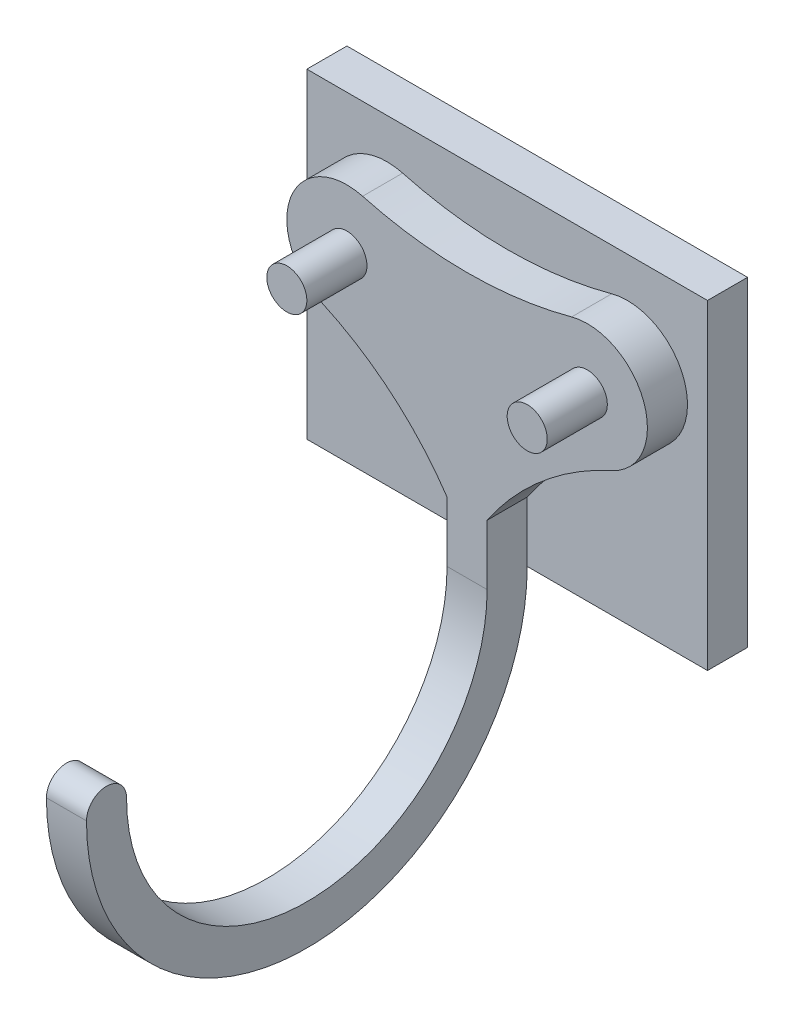
SolidWorks part; units mm, degrees
ref_plane "Front Plane" through (0, 0, 0) normal (0, 0, 1) x (1, 0, 0)
ref_plane "Top Plane" through (0, 0, 0) normal (0, 1, 0) x (1, 0, 0)
ref_plane "Right Plane" through (0, 0, 0) normal (1, 0, 0) x (0, 0, -1)
sketch "Sketch1" plane through (0, 0, 0) normal (0, 0, 1) x (1, 0, 0)
  line L0 (0, 0) -> (0, 12222.5331) construction
  line L1 (0, 0) -> (-12222.5331, 0) construction
  line L3 (-10, -8) -> (10, -8)
  line L4 (-10, -8) -> (-10, 8)
  line L5 (-10, 8) -> (10, 8)
  line L6 (10, -8) -> (10, 8)
  line L7 (-10, -8) -> (10, 8) construction
  line L8 (-10, 8) -> (10, -8) construction
  line L9 (-1, -8) -> (1, -8)
  line L10 (-1, -8) -> (-1, -5)
  line L12 (1, -8) -> (1, -5)
  line L13 (-1, -8) -> (1, -5) construction
  line L14 (-1, -5) -> (1, -8) construction
  circle A0 centre (6, 3) radius 1
  circle A1 centre (-6, 3) radius 1
  arc A2 (6, 0) -> (5.2174, 5.8961) centre (6, 3) ccw
  arc A3 (-5.2174, 5.8961) -> (-6, 0) centre (-6, 3) ccw
  arc A4 (-5.2174, 5.8961) -> (5.2174, 5.8961) centre (0, 25.2036) ccw
  arc A5 (-7.2385, 0.2676) -> (-1, -5) centre (-13.4311, -13.3945) cw
  arc A6 (7.2385, 0.2676) -> (1, -5) centre (13.4311, -13.3945) ccw
  point P14 (0, 0)
  point P22 (0, -6.5)
  dimension "D1" = 2
  dimension "D2" = 2
  dimension "D5" = 6
  dimension "D6" = 6
  dimension "D7" = 20
  dimension "D8" = 16
  dimension "D14" = 15
  dimension "D3" = 6
  dimension "D4" = 6
  dimension "D9" = 20
  dimension "D10" = 5
  dimension "D11" = 2
  dimension "D12" = 0
  dimension "D13" = 3
extrude "Boss-Extrude2" add sketch "Sketch1" along normal blind 2 contours A2 A6 L12 L3 L6 L5 L4 L10 A5 A3 A4 region at (-9.7439, 0, 0)
extrude "Boss-Extrude3" add sketch "Sketch1<5>" along normal blind 4 contours A6 A2 A4 A3 A5 L10 L3 L12 A1 A0 region at (0, 1.1623, 0)
sketch "Sketch1<5>" plane through (0, 0, 0) normal (0, 0, 1) x (1, 0, 0) same geometry as "Sketch1"
extrude "Boss-Extrude4" add sketch "Sketch1<6>" along normal blind 7 contours A1 | A0 region at (6, 3, 0) region at (-6, 3, 0)
sketch "Sketch1<6>" plane through (0, 0, 0) normal (0, 0, 1) x (1, 0, 0) same geometry as "Sketch1"
ref_plane "Plane1" through (0, 0, 13) normal (0, 0, 1) x (1, 0, 0)
ref_plane "Plane2" through (0, -8, 0) normal (0, -1, 0) x (-1, 0, 0)
ref_axis "Axis1" through (-9.9, -8, 13) along (1, 0, 0)
sketch "Sketch2" plane through (0, -8, 0) normal (0, -1, 0) x (1, 0, 0)
  line L0 (1, 4) -> (1, 2) construction
  line L1 (-1, 2) -> (1, 2)
  line L2 (-1, 2) -> (-1, 4)
  line L3 (-1, 4) -> (1, 4)
  line L4 (1, 2) -> (1, 4)
  line L5 (-1, 4) -> (1, 4) construction
revolve "Revolve1" add sketch "Sketch2" angle 180 about axis through (-9.9, -8, 13) along (1, 0, 0) reverse direction yes
sketch "Sketch3" plane through (-1, 0, 0) normal (-1, 0, 0) x (0, 0, 1)
  line L0 (22, -8) -> (24, -8) construction
  circle A0 centre (23, -8) radius 1
extrude "Boss-Extrude5" add sketch "Sketch3" against normal blind 2
